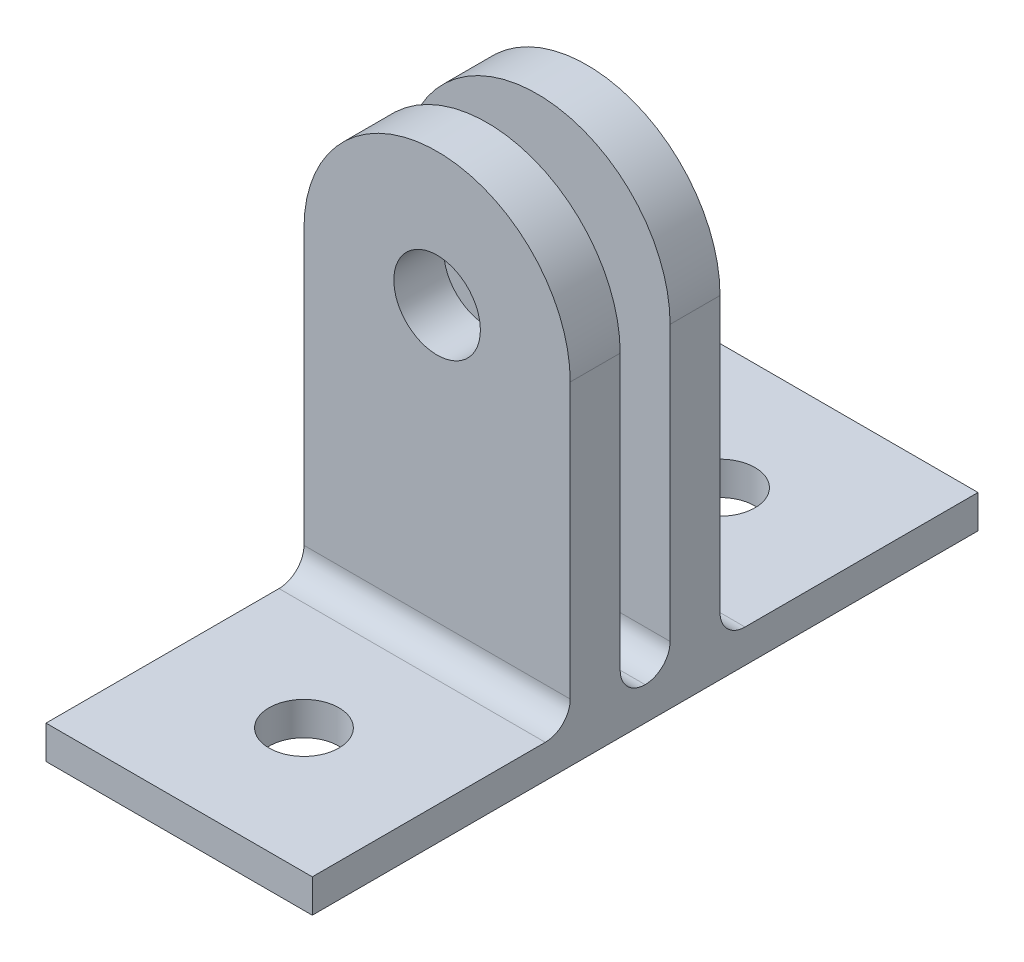
SolidWorks part; units mm, degrees
ref_plane "前基準面" through (0, 0, 0) normal (0, 0, 1) x (1, 0, 0)
ref_plane "上基準面" through (0, 0, 0) normal (0, 1, 0) x (1, 0, 0)
ref_plane "右基準面" through (0, 0, 0) normal (1, 0, 0) x (0, 0, -1)
sketch "草圖2" plane through (0, 0, 0) normal (0, 1, 0) x (1, 0, 0)
  line L0 (-18.1017, 0) -> (18.1017, 0) construction
  line L2 (-8, -20) -> (8, -20)
  line L3 (-8, -20) -> (-8, 20)
  line L4 (-8, 20) -> (8, 20)
  line L6 (0, 20) -> (0, -20) construction
  line L7 (-8, 0) -> (0, 0) construction
  line L9 (8, 20) -> (8, -20) construction
  line L11 (8, 20) -> (8, -20)
  point P1 (0, 0)
  point P4 (0, 0)
  point P9 (8, 20.1576)
  point P10 (8, -19.207)
  point P11 (8, -19.9159)
  point P12 (0, 0)
  dimension "D1" = 16
  dimension "D2" = 40
extrude "填料-伸長1" add sketch "草圖2" along normal blind 2
sketch "草圖4" plane through (0, 0, 0) normal (0, 0, 1) x (1, 0, 0)
  line L0 (0, -10.2424) -> (0, 10.2424) construction
  line L3 (8, 20) -> (-8, 20) construction
  line L4 (8, 20) -> (8, 2)
  line L5 (8, 2) -> (-8, 2)
  line L6 (-8, 20) -> (-8, 2)
  line L7 (0, 2) -> (0, 20) construction
  line L8 (8, 11) -> (-8, 11) construction
  arc A0 (-8, 20) -> (8, 20) centre (0, 20) cw
  circle A1 centre (0, 20) radius 2.6
  point P1 (0, 11)
  point P6 (0, 0)
  dimension "D2" = 5.2
  dimension "D1" = 18
extrude "填料-伸長2" add sketch "草圖4" along normal blind 3 from offset 1.5
mirror "鏡射1" about plane through (0, 0, 0) normal (0, 0, 1) of "填料-伸長2"
fillet "圓角2" radius 1.5 4 edges at (0, 2, -1.5) (0, 2, -4.5) (0, 2, 4.5) (0, 2, 1.5)
sketch "草圖5" plane through (0, 2, 0) normal (0, 1, 0) x (1, 0, 0)
  line L0 (-29.3899, 0) -> (29.3899, 0) construction
  line L2 (0, -21.7714) -> (0, 21.7714) construction
  circle A0 centre (0, -12.5) radius 2.1
  circle A1 centre (0, 12.5) radius 2.1
  point P6 (0, 0)
  point P7 (0, 0)
  point P9 (0, -12.8688)
  dimension "D1" = 4.2
  dimension "D2" = 25
extrude "除料-伸長1" cut sketch "草圖5" against normal through all
